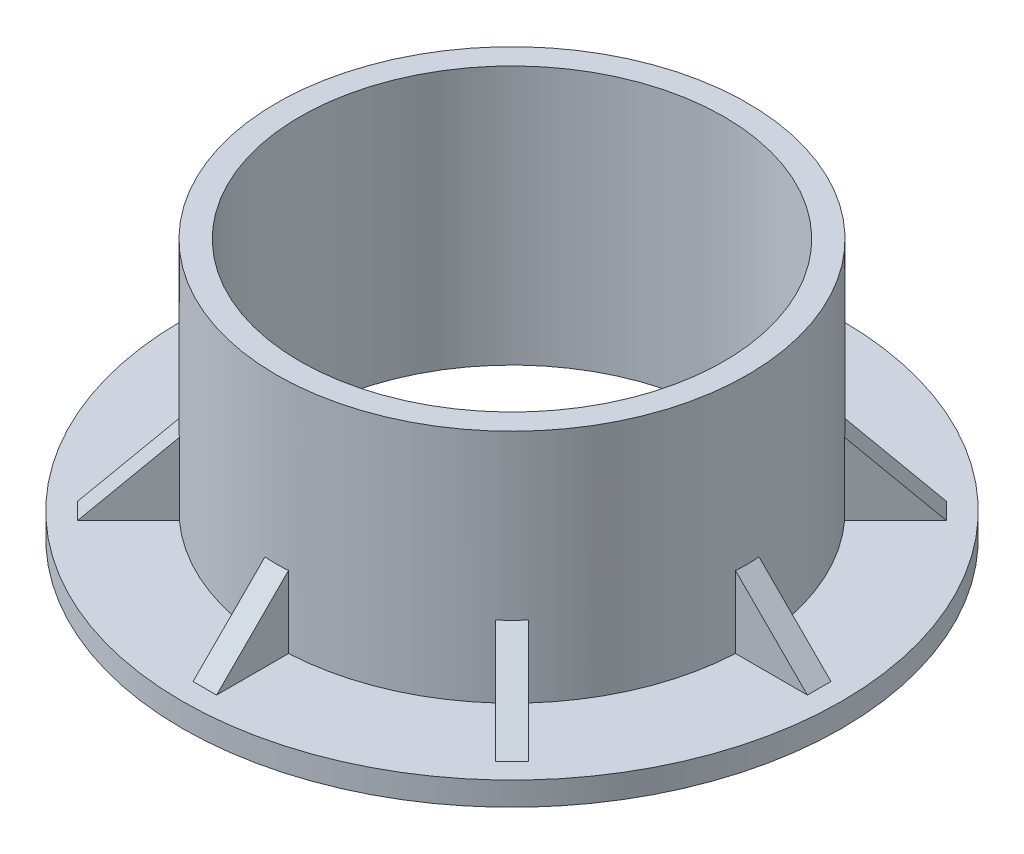
SolidWorks part; units mm, degrees
ref_plane "Front Plane" through (0, 0, 0) normal (0, 0, 1) x (1, 0, 0)
ref_plane "Top Plane" through (0, 0, 0) normal (0, 1, 0) x (1, 0, 0)
ref_plane "Right Plane" through (0, 0, 0) normal (1, 0, 0) x (0, 0, -1)
sketch "Sketch1" plane through (0, 0, 0) normal (0, 1, 0) x (1, 0, 0)
  circle A0 centre (0, 0) radius 50
  circle A1 centre (0, 0) radius 45
extrude "Boss-Extrude1" add sketch "Sketch1" along normal blind 50
sketch "Sketch2" plane through (0, 0, 0) normal (0, -1, 0) x (1, 0, 0)
  circle A0 centre (0, 0) radius 45 construction
  circle A1 centre (0, 0) radius 45
  circle A2 centre (0, 0) radius 70
extrude "Boss-Extrude2" add sketch "Sketch2" along normal blind 5
sketch "Sketch3" plane through (0, 0, 0) normal (1, 0, 0) x (0, 0, -1)
  line L0 (-52.1747, 13.0448) -> (-63.2248, 1.9947)
rib "Rib1" sketch "Sketch3" sketch "Sketch3" thickness 5 extrusion direction parallel to sketch draft on no parameters "D1"=5
sketch "Sketch4" plane through (0, 0, 0) normal (1, 0, 0) x (0, 0, -1)
  line L0 (0, -8.1441) -> (0, 63.3967) construction
pattern_circular "CirPattern1" count 8 over 360 about axis through (0, -8.1441, 0) along (0, 1, 0) of "Rib1" reverse direction yes
